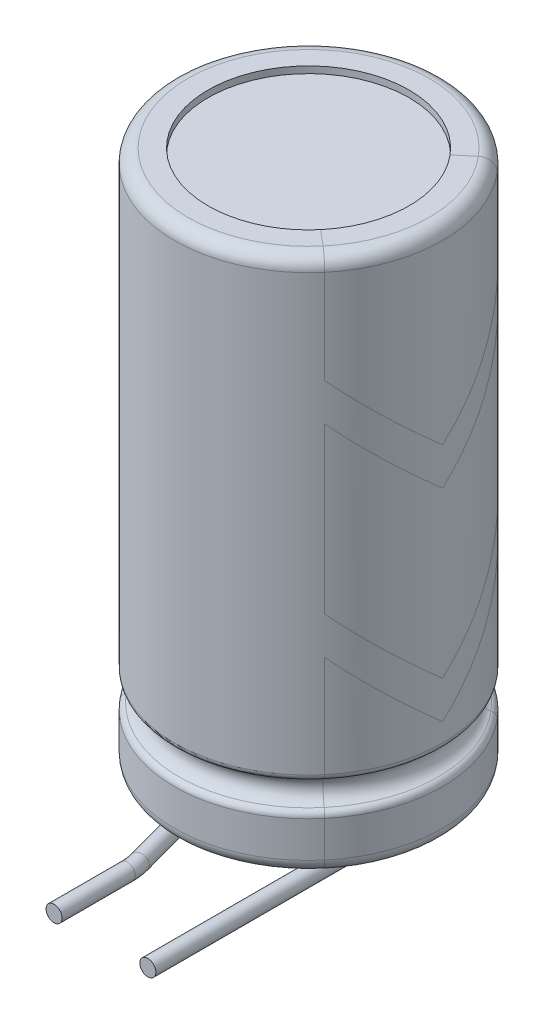
SolidWorks part; units mm, degrees
ref_plane "Front" through (0, 0, 0) normal (0, 0, 1) x (1, 0, 0)
ref_plane "Top" through (0, 0, 0) normal (0, 1, 0) x (1, 0, 0)
ref_plane "Right" through (0, 0, 0) normal (1, 0, 0) x (0, 0, -1)
sketch "Sketch1" plane through (0, 0, 0) normal (0, 1, 0) x (1, 0, 0)
  circle A0 centre (0, 0) radius 5
  dimension "D1" = 10
extrude "Base-Extrude" add sketch "Sketch1" along normal blind 20
sketch "Sketch2" plane through (0, 0, 0) normal (1, 0, 0) x (0, 0, -1)
  line L0 (-5, 20) -> (-5, 0) construction
  line L1 (-5, 3.0532) -> (-5, 2.0532)
  line L2 (0, 0) -> (0, 7.7627) construction
  line L3 (0, 20) -> (0, 0) construction
  arc A0 (-5, 2.0532) -> (-5, 3.0532) centre (-5, 2.5532) ccw
  dimension "D1" = 0.5
revolve "Cut-Revolve1" cut sketch "Sketch2" angle 360 about L2
sketch "Sketch4" plane through (0, 0, 0) normal (0, -1, 0) x (1, 0, 0)
  circle A0 centre (0, 0) radius 3.75
  dimension "D1" = 7.5
extrude "Cut-Extrude1" cut sketch "Sketch4" against normal blind 0.25
sketch "Sketch3" plane through (0, 0.25, 0) normal (0, -1, 0) x (1, 0, 0)
  circle A0 centre (-1.75, 0) radius 0.3
  circle A1 centre (1.75, 0) radius 0.3
  dimension "D1" = 0.6
  dimension "D2" = 1.75
  dimension "D3" = 3.5
extrude "Boss-Extrude1" [suppressed] add sketch "Sketch3" along normal blind 29
sketch "Sketch5" [suppressed] plane through (0, -28.75, 0) normal (0, -1, 0) x (1, 0, 0)
  circle A1 centre (1.75, 0) radius 0.3
  circle A2 centre (1.75, 0) radius 0.3
  dimension "D1" = 0
extrude "Cut-Extrude2" [suppressed] cut sketch "Sketch5" against normal blind 5
sketch "Sketch6" plane through (0, 20, 0) normal (0, 1, 0) x (-1, 0, 0)
  circle A0 centre (0, 0) radius 3.75
  dimension "D1" = 7.5
extrude "Cut-Extrude3" cut sketch "Sketch6" against normal blind 0.25
ref_plane "Plane1" through (5, 0, 0) normal (1, 0, 0) x (0, 0, -1)
sketch "Sketch10" plane through (0, 20, 0) normal (0, 1, 0) x (1, 0, 0)
  line L0 (3.8242, 3.2211) -> (0, 0)
  line L1 (3.8242, -3.2211) -> (0, 0)
  line L2 (0, 0) -> (5, 0) construction
  circle A2 centre (0, 0) radius 5 construction
  arc A3 (3.8242, -3.2211) -> (3.8242, 3.2211) centre (0, 0) ccw
  dimension "D1" = 7
split line "Split Line2"
sketch "Sketch8" plane through (5, 0, 0) normal (1, 0, 0) x (0, 0, -1)
  line L0 (5, 20) -> (-5, 20) construction
  line L2 (-3.5, 20) -> (-3.5, 16)
  line L3 (-3.5, 20) -> (3.5, 20)
  line L4 (3.5, 20) -> (3.5, 16)
  line L6 (0, 3.0532) -> (0, 25.4) construction
  line L7 (3.5, 8.4532) -> (0, 5.3532)
  line L8 (0, 5.3532) -> (-3.5, 8.4532)
  line L9 (3.5, 7.0532) -> (0, 3.9532)
  line L10 (0, 3.9532) -> (-3.5, 7.0532)
  line L11 (3.5, 7.0532) -> (3.5, 3.0532)
  line L12 (-3.5, 7.0532) -> (-3.5, 3.0532)
  line L14 (-3.5, 3.0532) -> (3.5, 3.0532)
  line L16 (2.4158, 20) -> (-2.4158, 20) construction
  line L17 (-5, 3.0532) -> (5, 3.0532) construction
  line L19 (-3.5, 16) -> (0, 12.9)
  line L20 (0, 12.9) -> (3.5, 16)
  line L21 (3.5, 14.6) -> (0, 11.5)
  line L22 (0, 11.5) -> (-3.5, 14.6)
  line L24 (-3.5, 14.6) -> (-3.5, 8.4532)
  line L25 (3.5, 14.6) -> (3.5, 8.4532)
  line L26 (3.5, 8.4532) -> (3.5, 7.0532) construction
  line L27 (3.5, 16) -> (3.5, 14.6) construction
  dimension "D1" = 7
  dimension "D2" = 1.4
  dimension "D3" = 4.5
  dimension "D4" = 4
  dimension "D5" = 4
wrap "Wrap3" sketch "Sketch8" wrap type scribe source sketch "Sketch8" face at (0, 20, 0)
sketch "Sketch11" plane through (5, 0, 0) normal (1, 0, 0) x (0, 0, -1)
  line L3 (-3.2211, 2.0532) -> (3.2211, 2.0532)
  line L6 (-3.2211, 2.0532) -> (-3.2211, 0)
  line L7 (-3.2211, 0) -> (3.2211, 0)
  line L8 (3.2211, 2.0532) -> (3.2211, 0)
  line L9 (-5, 0) -> (5, 0) construction
split line "Split Line3"
fillet "Fillet3" radius 0.5 6 edges at (5, 20, 0) (5, 0, 0) (0, 0, 5) (-5, 0, 0) (0, 0, -5) (-5, 20, 0)
fillet "Fillet4" radius 0.25 6 edges at (5, 2.0532, 0) (0, 2.0532, -5) (-5, 2.0532, 0) (0, 2.0532, 5) (5, 3.0532, 0) (-5, 3.0532, 0)
sketch3d "3DSketch1"
  point P0 (0, -3.175, 0)
  dimension "D1" = 3.175
other "CPoint1" parameters "Diameter"=2.3813, "StubLength"=0
ref_axis "Axis1" through (0, -13.175, 0) along (0, 1, 0)
sketch "Sketch12" plane through (0, 0.25, 0) normal (0, -1, 0) x (-1, 0, 0)
  circle A0 centre (-2.5, 0) radius 0.3
  dimension "D1" = 2.5
sketch "Sketch14" plane through (0, 0, 0) normal (1, 0, 0) x (0, 0, -1)
  line L0 (0, 0.25) -> (0, -0.5)
  line L1 (-0.3, 0.25) -> (0.3, 0.25) construction
  line L2 (-0.5, -1) -> (-8.5, -1)
  line L4 (-2.899, 0) -> (2.899, 0) construction
  arc A0 (0, -0.5) -> (-0.5, -1) centre (-0.5, -0.5) cw
  dimension "D2" = 0.5
  dimension "D1" = 0.5
  dimension "D3" = 8
sweep "Sweep1" add profiles "Sketch12" path "Sketch14"
sketch "Sketch17" plane through (0, 0.25, 0) normal (0, -1, 0) x (-1, 0, 0)
  circle A0 centre (2.5, 0) radius 0.3
  dimension "D1" = 0.6
  dimension "D2" = 2.5
sketch3d "3DSketch2"
  line L0 (-2.5, 0.25, 0) -> (-2.5, -0.5, 0)
  line L1 (-2.3684, -1, 0.4824) -> (-1.0705, -1, 5.2416)
  line L2 (-1, -1, 5.7678) -> (-1, -1, 8.5)
  arc A0 (-2.5, -0.5, 0) -> (-2.3684, -1, 0.4824) centre (-2.3684, -0.5, 0.4824) cw
  arc A3 (-1.0705, -1, 5.2416) -> (-1, -1, 5.7678) centre (-3, -1, 5.7678) ccw
  point P4 (-2.8508, -0.5, 0.6139)
  point P10 (-1, -1, 5.5)
  point P11 (-3, -3, 5.7678)
  dimension "D3" = 0.5
  dimension "D4" = 2
  dimension "D1" = 0.75
  dimension "D2" = 1.25
  dimension "D5" = 3
sweep "Sweep3" add profiles "Sketch17" path "3DSketch2"
